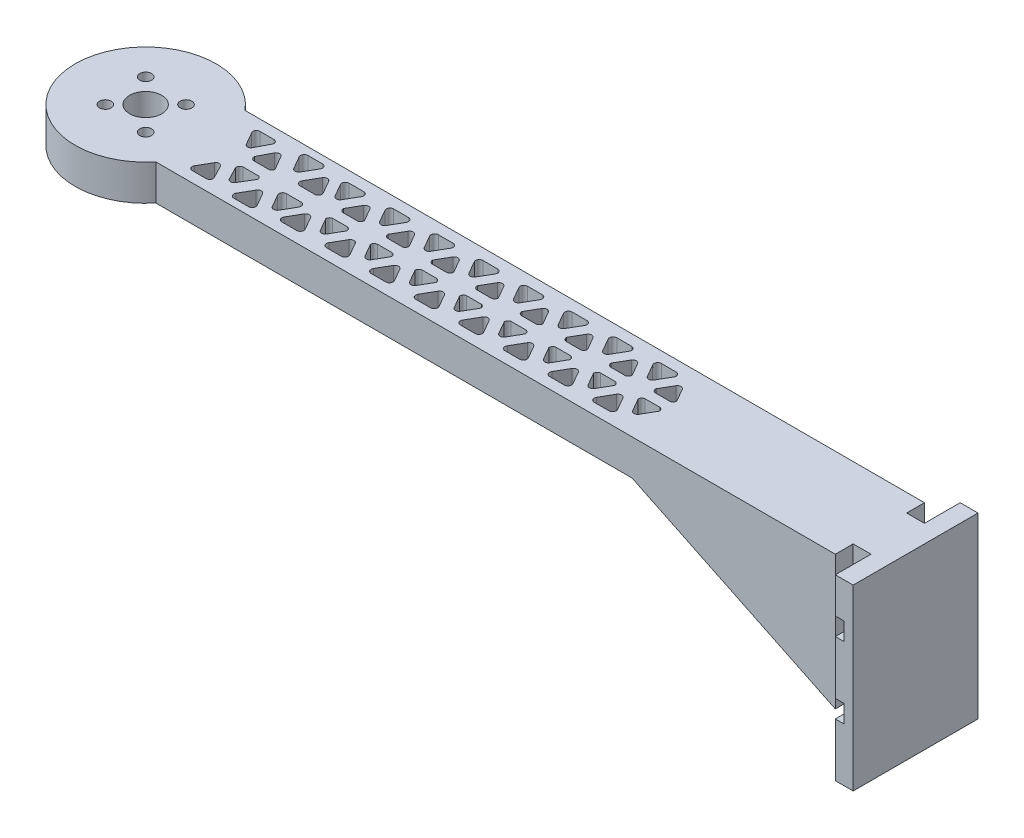
SolidWorks part; units mm, degrees
note: The reader was unsure of these and kept them because the rebuilt part matched: shared geometry of "Sketch2<4>".
ref_plane "Front Plane" through (0, 0, 0) normal (0, 0, 1) x (1, 0, 0)
ref_plane "Top Plane" through (0, 0, 0) normal (0, 1, 0) x (1, 0, 0)
ref_plane "Right Plane" through (0, 0, 0) normal (1, 0, 0) x (0, 0, -1)
sketch "Sketch1" plane through (0, 0, 0) normal (0, 1, 0) x (1, 0, 0)
  line L0 (19.7015, -0.0803) -> (215.7812, -0.0803) construction
  line L1 (15.2517, 12.4197) -> (215.7812, 12.4197)
  line L2 (15.2517, -12.5803) -> (215.7812, -12.5803)
  line L3 (215.7812, 12.4197) -> (215.7812, -12.5803)
  line L4 (22.4549, 9.4197) -> (26.384, 9.4197)
  line L5 (27.2449, 8.0014) -> (25.383, 4.4231)
  line L6 (23.682, 4.3855) -> (21.6147, 7.9638)
  line L7 (29.7182, 6.2554) -> (27.8031, 2.5747)
  line L8 (33.7755, 2.3958) -> (31.5736, 6.0947)
  line L9 (28.7602, 1.4197) -> (33.171, 1.4197)
  line L10 (37.9612, 5.1841) -> (40.0285, 8.7624)
  line L11 (34.1207, 8.7624) -> (36.188, 5.1841)
  line L12 (39.1419, 10.2986) -> (35.0073, 10.2986)
  line L13 (45.3949, 1.819) -> (41.2604, 1.819)
  line L14 (40.3733, 3.3543) -> (42.441, 6.9413)
  line L15 (44.2142, 6.9413) -> (46.2815, 3.363)
  line L16 (47.5213, 9.3393) -> (51.6558, 9.3393)
  line L17 (52.5425, 7.8032) -> (50.4752, 4.2249)
  line L18 (48.702, 4.2249) -> (46.6347, 7.8032)
  line L19 (54.955, 5.982) -> (52.8877, 2.4037)
  line L20 (58.7955, 2.3958) -> (56.7282, 5.982)
  line L21 (53.7743, 1.3393) -> (57.9089, 1.3393)
  line L22 (60.0313, 9.3393) -> (64.1658, 9.3393)
  line L23 (65.0525, 7.8032) -> (62.9852, 4.2249)
  line L24 (61.212, 4.2249) -> (59.1447, 7.8032)
  line L25 (67.465, 5.982) -> (65.3977, 2.4037)
  line L26 (71.3055, 2.3958) -> (69.2382, 5.982)
  line L27 (66.2843, 1.3393) -> (70.4189, 1.3393)
  line L28 (72.5413, 9.3393) -> (76.6758, 9.3393)
  line L29 (77.5625, 7.8032) -> (75.4952, 4.2249)
  line L30 (73.722, 4.2249) -> (71.6547, 7.8032)
  line L31 (79.975, 5.982) -> (77.9077, 2.4037)
  line L32 (83.8155, 2.3958) -> (81.7482, 5.982)
  line L33 (78.7943, 1.3393) -> (82.9289, 1.3393)
  line L34 (85.0513, 9.3393) -> (89.1858, 9.3393)
  line L35 (90.0725, 7.8032) -> (88.0052, 4.2249)
  line L36 (86.232, 4.2249) -> (84.1647, 7.8032)
  line L37 (92.485, 5.982) -> (90.4177, 2.4037)
  line L38 (96.3255, 2.3958) -> (94.2582, 5.982)
  line L39 (91.3043, 1.3393) -> (95.4389, 1.3393)
  line L40 (91.3043, -1.5) -> (95.4389, -1.5)
  line L41 (96.3255, -2.5565) -> (94.2582, -6.1427)
  line L42 (92.485, -6.1427) -> (90.4177, -2.5644)
  line L43 (86.232, -4.3855) -> (84.1647, -7.9638)
  line L44 (90.0725, -7.9638) -> (88.0052, -4.3855)
  line L45 (85.0513, -9.5) -> (89.1858, -9.5)
  line L46 (78.7943, -1.5) -> (82.9289, -1.5)
  line L47 (83.8155, -2.5565) -> (81.7482, -6.1427)
  line L48 (79.975, -6.1427) -> (77.9077, -2.5644)
  line L49 (73.722, -4.3855) -> (71.6547, -7.9638)
  line L50 (77.5625, -7.9638) -> (75.4952, -4.3855)
  line L51 (72.5413, -9.5) -> (76.6758, -9.5)
  line L52 (66.2843, -1.5) -> (70.4189, -1.5)
  line L53 (71.3055, -2.5565) -> (69.2382, -6.1427)
  line L54 (67.465, -6.1427) -> (65.3977, -2.5644)
  line L55 (61.212, -4.3855) -> (59.1447, -7.9638)
  line L56 (65.0525, -7.9638) -> (62.9852, -4.3855)
  line L57 (60.0313, -9.5) -> (64.1658, -9.5)
  line L58 (53.7743, -1.5) -> (57.9089, -1.5)
  line L59 (58.7955, -2.5565) -> (56.7282, -6.1427)
  line L60 (54.955, -6.1427) -> (52.8877, -2.5644)
  line L61 (48.702, -4.3855) -> (46.6347, -7.9638)
  line L62 (52.5425, -7.9638) -> (50.4752, -4.3855)
  line L63 (47.5213, -9.5) -> (51.6558, -9.5)
  line L64 (44.2142, -7.1019) -> (46.2815, -3.5236)
  line L65 (40.3733, -3.5149) -> (42.441, -7.1019)
  line L66 (45.3949, -1.9796) -> (41.2604, -1.9796)
  line L67 (39.1419, -10.4593) -> (35.0073, -10.4593)
  line L68 (34.1207, -8.9231) -> (36.188, -5.3448)
  line L69 (37.9612, -5.3448) -> (40.0285, -8.9231)
  line L70 (28.7602, -1.5803) -> (33.171, -1.5803)
  line L71 (33.7755, -2.5565) -> (31.5736, -6.2554)
  line L72 (29.7182, -6.4161) -> (27.8031, -2.7354)
  line L73 (23.682, -4.5462) -> (21.6147, -8.1245)
  line L74 (27.2449, -8.1621) -> (25.383, -4.5837)
  line L75 (22.4549, -9.5803) -> (26.384, -9.5803)
  line L76 (-0.0803, -16.7095) -> (-0.0803, 16.5488) construction
  line L77 (11.7312, -11.8919) -> (-11.8919, 11.7312) construction
  line L78 (-12.5321, -12.5321) -> (12.3715, 12.3715) construction
  line L79 (97.5613, 9.3393) -> (101.6958, 9.3393)
  line L80 (102.5825, 7.8032) -> (100.5152, 4.2249)
  line L81 (98.742, 4.2249) -> (96.6747, 7.8032)
  line L82 (104.995, 5.982) -> (102.9277, 2.4037)
  line L83 (108.8355, 2.3958) -> (106.7682, 5.982)
  line L84 (103.8143, 1.3393) -> (107.9489, 1.3393)
  line L85 (110.0713, 9.3393) -> (114.2058, 9.3393)
  line L86 (115.0925, 7.8032) -> (113.0252, 4.2249)
  line L87 (111.252, 4.2249) -> (109.1847, 7.8032)
  line L88 (117.505, 5.982) -> (115.4377, 2.4037)
  line L89 (121.3455, 2.3958) -> (119.2782, 5.982)
  line L90 (116.3243, 1.3393) -> (120.4589, 1.3393)
  line L91 (122.5813, 9.3393) -> (126.7158, 9.3393)
  line L92 (127.6025, 7.8032) -> (125.5352, 4.2249)
  line L93 (123.762, 4.2249) -> (121.6947, 7.8032)
  line L94 (130.015, 5.982) -> (127.9477, 2.4037)
  line L95 (133.8555, 2.3958) -> (131.7882, 5.982)
  line L96 (128.8343, 1.3393) -> (132.9689, 1.3393)
  line L97 (135.0913, 9.3393) -> (139.2258, 9.3393)
  line L98 (140.1125, 7.8032) -> (138.0452, 4.2249)
  line L99 (136.272, 4.2249) -> (134.2047, 7.8032)
  line L100 (142.525, 5.982) -> (140.4577, 2.4037)
  line L101 (146.3655, 2.3958) -> (144.2982, 5.982)
  line L102 (141.3443, 1.3393) -> (145.4789, 1.3393)
  line L139 (141.3443, -1.5) -> (145.4789, -1.5)
  line L140 (146.3655, -2.5565) -> (144.2982, -6.1427)
  line L141 (142.525, -6.1427) -> (140.4577, -2.5644)
  line L142 (136.272, -4.3855) -> (134.2047, -7.9638)
  line L143 (140.1125, -7.9638) -> (138.0452, -4.3855)
  line L144 (135.0913, -9.5) -> (139.2258, -9.5)
  line L145 (128.8343, -1.5) -> (132.9689, -1.5)
  line L146 (133.8555, -2.5565) -> (131.7882, -6.1427)
  line L147 (130.015, -6.1427) -> (127.9477, -2.5644)
  line L148 (123.762, -4.3855) -> (121.6947, -7.9638)
  line L149 (127.6025, -7.9638) -> (125.5352, -4.3855)
  line L150 (122.5813, -9.5) -> (126.7158, -9.5)
  line L151 (116.3243, -1.5) -> (120.4589, -1.5)
  line L152 (121.3455, -2.5565) -> (119.2782, -6.1427)
  line L153 (117.505, -6.1427) -> (115.4377, -2.5644)
  line L154 (111.252, -4.3855) -> (109.1847, -7.9638)
  line L155 (115.0925, -7.9638) -> (113.0252, -4.3855)
  line L156 (110.0713, -9.5) -> (114.2058, -9.5)
  line L157 (103.8143, -1.5) -> (107.9489, -1.5)
  line L158 (108.8355, -2.5565) -> (106.7682, -6.1427)
  line L159 (104.995, -6.1427) -> (102.9277, -2.5644)
  line L160 (98.742, -4.3855) -> (96.6747, -7.9638)
  line L161 (102.5825, -7.9638) -> (100.5152, -4.3855)
  line L162 (97.5613, -9.5) -> (101.6958, -9.5)
  line L163 (147.6013, 9.3393) -> (151.7358, 9.3393) [skipped]
  line L164 (152.6225, 7.8032) -> (150.5552, 4.2249) [skipped]
  line L165 (148.782, 4.2249) -> (146.7147, 7.8032) [skipped]
  line L166 (155.035, 5.982) -> (152.9677, 2.4037) [skipped]
  line L167 (158.8755, 2.3958) -> (156.8082, 5.982) [skipped]
  line L168 (153.8543, 1.3393) -> (157.9889, 1.3393) [skipped]
  line L169 (160.1113, 9.3393) -> (164.2458, 9.3393) [skipped]
  line L170 (165.1325, 7.8032) -> (163.0652, 4.2249) [skipped]
  line L171 (161.292, 4.2249) -> (159.2247, 7.8032) [skipped]
  line L172 (167.545, 5.982) -> (165.4777, 2.4037) [skipped]
  line L173 (171.3855, 2.3958) -> (169.3182, 5.982) [skipped]
  line L174 (166.3643, 1.3393) -> (170.4989, 1.3393) [skipped]
  line L175 (172.6213, 9.3393) -> (176.7558, 9.3393) [skipped]
  line L176 (177.6425, 7.8032) -> (175.5752, 4.2249) [skipped]
  line L177 (173.802, 4.2249) -> (171.7347, 7.8032) [skipped]
  line L178 (180.055, 5.982) -> (177.9877, 2.4037) [skipped]
  line L179 (183.8955, 2.3958) -> (181.8282, 5.982) [skipped]
  line L180 (178.8743, 1.3393) -> (183.0089, 1.3393) [skipped]
  circle A0 centre (-0.0803, -0.0803) radius 19.7818
  arc A1 (25.383, 4.4231) -> (23.682, 4.3855) centre (24.5222, 4.871) cw
  arc A2 (22.4549, 9.4197) -> (21.6147, 7.9638) centre (22.4549, 8.4493) ccw
  arc A3 (26.384, 9.4197) -> (27.2449, 8.0014) centre (26.384, 8.4493) cw
  arc A4 (33.171, 1.4197) -> (33.7755, 2.3958) centre (32.7524, 2.3541) ccw
  arc A5 (31.5736, 6.0947) -> (29.7182, 6.2554) centre (30.6092, 5.7508) ccw
  arc A6 (28.7602, 1.4197) -> (27.8031, 2.5747) centre (28.8569, 2.4738) cw
  arc A7 (35.0073, 10.2986) -> (34.1207, 8.7624) centre (35.0073, 9.2747) ccw
  arc A8 (39.1419, 10.2986) -> (40.0285, 8.7624) centre (39.1419, 9.2747) cw
  arc A9 (36.188, 5.1841) -> (37.9612, 5.1841) centre (37.0746, 5.6963) ccw
  arc A10 (45.3949, 1.819) -> (46.2815, 3.363) centre (45.3995, 2.8429) ccw
  arc A11 (42.441, 6.9413) -> (44.2142, 6.9413) centre (43.3276, 6.4291) cw
  arc A12 (41.2604, 1.819) -> (40.3733, 3.3543) centre (41.2604, 2.8429) cw
  arc A13 (50.4752, 4.2249) -> (48.702, 4.2249) centre (49.5886, 4.7371) cw
  arc A14 (47.5213, 9.3393) -> (46.6347, 7.8032) centre (47.5213, 8.3154) ccw
  arc A15 (51.6558, 9.3393) -> (52.5425, 7.8032) centre (51.6558, 8.3154) cw
  arc A16 (57.9089, 1.3393) -> (58.7955, 2.3958) centre (57.7724, 2.3541) ccw
  arc A17 (56.7282, 5.982) -> (54.955, 5.982) centre (55.8416, 5.4698) ccw
  arc A18 (53.7743, 1.3393) -> (52.8877, 2.4037) centre (53.9105, 2.3542) cw
  arc A19 (62.9852, 4.2249) -> (61.212, 4.2249) centre (62.0986, 4.7371) cw
  arc A20 (60.0313, 9.3393) -> (59.1447, 7.8032) centre (60.0313, 8.3154) ccw
  arc A21 (64.1658, 9.3393) -> (65.0525, 7.8032) centre (64.1658, 8.3154) cw
  arc A22 (70.4189, 1.3393) -> (71.3055, 2.3958) centre (70.2824, 2.3541) ccw
  arc A23 (69.2382, 5.982) -> (67.465, 5.982) centre (68.3516, 5.4698) ccw
  arc A24 (66.2843, 1.3393) -> (65.3977, 2.4037) centre (66.4205, 2.3542) cw
  arc A25 (75.4952, 4.2249) -> (73.722, 4.2249) centre (74.6086, 4.7371) cw
  arc A26 (72.5413, 9.3393) -> (71.6547, 7.8032) centre (72.5413, 8.3154) ccw
  arc A27 (76.6758, 9.3393) -> (77.5625, 7.8032) centre (76.6758, 8.3154) cw
  arc A28 (82.9289, 1.3393) -> (83.8155, 2.3958) centre (82.7924, 2.3541) ccw
  arc A29 (81.7482, 5.982) -> (79.975, 5.982) centre (80.8616, 5.4698) ccw
  arc A30 (78.7943, 1.3393) -> (77.9077, 2.4037) centre (78.9305, 2.3542) cw
  arc A31 (88.0052, 4.2249) -> (86.232, 4.2249) centre (87.1186, 4.7371) cw
  arc A32 (85.0513, 9.3393) -> (84.1647, 7.8032) centre (85.0513, 8.3154) ccw
  arc A33 (89.1858, 9.3393) -> (90.0725, 7.8032) centre (89.1858, 8.3154) cw
  arc A34 (95.4389, 1.3393) -> (96.3255, 2.3958) centre (95.3024, 2.3541) ccw
  arc A35 (94.2582, 5.982) -> (92.485, 5.982) centre (93.3716, 5.4698) ccw
  arc A36 (91.3043, 1.3393) -> (90.4177, 2.4037) centre (91.4405, 2.3542) cw
  arc A37 (91.3043, -1.5) -> (90.4177, -2.5644) centre (91.4405, -2.5148) ccw
  arc A38 (94.2582, -6.1427) -> (92.485, -6.1427) centre (93.3716, -5.6305) cw
  arc A39 (95.4389, -1.5) -> (96.3255, -2.5565) centre (95.3024, -2.5148) cw
  arc A40 (89.1858, -9.5) -> (90.0725, -7.9638) centre (89.1858, -8.4761) ccw
  arc A41 (85.0513, -9.5) -> (84.1647, -7.9638) centre (85.0513, -8.4761) cw
  arc A42 (88.0052, -4.3855) -> (86.232, -4.3855) centre (87.1186, -4.8978) ccw
  arc A43 (78.7943, -1.5) -> (77.9077, -2.5644) centre (78.9305, -2.5148) ccw
  arc A44 (81.7482, -6.1427) -> (79.975, -6.1427) centre (80.8616, -5.6305) cw
  arc A45 (82.9289, -1.5) -> (83.8155, -2.5565) centre (82.7924, -2.5148) cw
  arc A46 (76.6758, -9.5) -> (77.5625, -7.9638) centre (76.6758, -8.4761) ccw
  arc A47 (72.5413, -9.5) -> (71.6547, -7.9638) centre (72.5413, -8.4761) cw
  arc A48 (75.4952, -4.3855) -> (73.722, -4.3855) centre (74.6086, -4.8978) ccw
  arc A49 (66.2843, -1.5) -> (65.3977, -2.5644) centre (66.4205, -2.5148) ccw
  arc A50 (69.2382, -6.1427) -> (67.465, -6.1427) centre (68.3516, -5.6305) cw
  arc A51 (70.4189, -1.5) -> (71.3055, -2.5565) centre (70.2824, -2.5148) cw
  arc A52 (64.1658, -9.5) -> (65.0525, -7.9638) centre (64.1658, -8.4761) ccw
  arc A53 (60.0313, -9.5) -> (59.1447, -7.9638) centre (60.0313, -8.4761) cw
  arc A54 (62.9852, -4.3855) -> (61.212, -4.3855) centre (62.0986, -4.8978) ccw
  arc A55 (53.7743, -1.5) -> (52.8877, -2.5644) centre (53.9105, -2.5148) ccw
  arc A56 (56.7282, -6.1427) -> (54.955, -6.1427) centre (55.8416, -5.6305) cw
  arc A57 (57.9089, -1.5) -> (58.7955, -2.5565) centre (57.7724, -2.5148) cw
  arc A58 (51.6558, -9.5) -> (52.5425, -7.9638) centre (51.6558, -8.4761) ccw
  arc A59 (47.5213, -9.5) -> (46.6347, -7.9638) centre (47.5213, -8.4761) cw
  arc A60 (50.4752, -4.3855) -> (48.702, -4.3855) centre (49.5886, -4.8978) ccw
  arc A61 (41.2604, -1.9796) -> (40.3733, -3.5149) centre (41.2604, -3.0036) ccw
  arc A62 (42.441, -7.1019) -> (44.2142, -7.1019) centre (43.3276, -6.5897) ccw
  arc A63 (45.3949, -1.9796) -> (46.2815, -3.5236) centre (45.3995, -3.0036) cw
  arc A64 (36.188, -5.3448) -> (37.9612, -5.3448) centre (37.0746, -5.857) cw
  arc A65 (39.1419, -10.4593) -> (40.0285, -8.9231) centre (39.1419, -9.4353) ccw
  arc A66 (35.0073, -10.4593) -> (34.1207, -8.9231) centre (35.0073, -9.4353) cw
  arc A67 (28.7602, -1.5803) -> (27.8031, -2.7354) centre (28.8569, -2.6345) ccw
  arc A68 (31.5736, -6.2554) -> (29.7182, -6.4161) centre (30.6092, -5.9115) cw
  arc A69 (33.171, -1.5803) -> (33.7755, -2.5565) centre (32.7524, -2.5148) cw
  arc A70 (26.384, -9.5803) -> (27.2449, -8.1621) centre (26.384, -8.61) ccw
  arc A71 (22.4549, -9.5803) -> (21.6147, -8.1245) centre (22.4549, -8.61) cw
  arc A72 (25.383, -4.5837) -> (23.682, -4.5462) centre (24.5222, -5.0316) ccw
  circle A73 centre (-6.7979, 6.6372) radius 1.65
  circle A74 centre (5.5765, 5.5765) radius 1.65
  circle A75 centre (6.6372, -6.7979) radius 1.65
  circle A76 centre (-5.7372, -5.7372) radius 1.65
  circle A77 centre (-0.0803, -0.0803) radius 4.5
  arc A78 (100.5152, 4.2249) -> (98.742, 4.2249) centre (99.6286, 4.7371) cw
  arc A79 (97.5613, 9.3393) -> (96.6747, 7.8032) centre (97.5613, 8.3154) ccw
  arc A80 (101.6958, 9.3393) -> (102.5825, 7.8032) centre (101.6958, 8.3154) cw
  arc A81 (107.9489, 1.3393) -> (108.8355, 2.3958) centre (107.8124, 2.3541) ccw
  arc A82 (106.7682, 5.982) -> (104.995, 5.982) centre (105.8816, 5.4698) ccw
  arc A83 (103.8143, 1.3393) -> (102.9277, 2.4037) centre (103.9505, 2.3542) cw
  arc A84 (113.0252, 4.2249) -> (111.252, 4.2249) centre (112.1386, 4.7371) cw
  arc A85 (110.0713, 9.3393) -> (109.1847, 7.8032) centre (110.0713, 8.3154) ccw
  arc A86 (114.2058, 9.3393) -> (115.0925, 7.8032) centre (114.2058, 8.3154) cw
  arc A87 (120.4589, 1.3393) -> (121.3455, 2.3958) centre (120.3224, 2.3541) ccw
  arc A88 (119.2782, 5.982) -> (117.505, 5.982) centre (118.3916, 5.4698) ccw
  arc A89 (116.3243, 1.3393) -> (115.4377, 2.4037) centre (116.4605, 2.3542) cw
  arc A90 (125.5352, 4.2249) -> (123.762, 4.2249) centre (124.6486, 4.7371) cw
  arc A91 (122.5813, 9.3393) -> (121.6947, 7.8032) centre (122.5813, 8.3154) ccw
  arc A92 (126.7158, 9.3393) -> (127.6025, 7.8032) centre (126.7158, 8.3154) cw
  arc A93 (132.9689, 1.3393) -> (133.8555, 2.3958) centre (132.8324, 2.3541) ccw
  arc A94 (131.7882, 5.982) -> (130.015, 5.982) centre (130.9016, 5.4698) ccw
  arc A95 (128.8343, 1.3393) -> (127.9477, 2.4037) centre (128.9705, 2.3542) cw
  arc A96 (138.0452, 4.2249) -> (136.272, 4.2249) centre (137.1586, 4.7371) cw
  arc A97 (135.0913, 9.3393) -> (134.2047, 7.8032) centre (135.0913, 8.3154) ccw
  arc A98 (139.2258, 9.3393) -> (140.1125, 7.8032) centre (139.2258, 8.3154) cw
  arc A99 (145.4789, 1.3393) -> (146.3655, 2.3958) centre (145.3424, 2.3541) ccw
  arc A100 (144.2982, 5.982) -> (142.525, 5.982) centre (143.4116, 5.4698) ccw
  arc A101 (141.3443, 1.3393) -> (140.4577, 2.4037) centre (141.4805, 2.3542) cw
  arc A138 (141.3443, -1.5) -> (140.4577, -2.5644) centre (141.4805, -2.5148) ccw
  arc A139 (144.2982, -6.1427) -> (142.525, -6.1427) centre (143.4116, -5.6305) cw
  arc A140 (145.4789, -1.5) -> (146.3655, -2.5565) centre (145.3424, -2.5148) cw
  arc A141 (139.2258, -9.5) -> (140.1125, -7.9638) centre (139.2258, -8.4761) ccw
  arc A142 (135.0913, -9.5) -> (134.2047, -7.9638) centre (135.0913, -8.4761) cw
  arc A143 (138.0452, -4.3855) -> (136.272, -4.3855) centre (137.1586, -4.8978) ccw
  arc A144 (128.8343, -1.5) -> (127.9477, -2.5644) centre (128.9705, -2.5148) ccw
  arc A145 (131.7882, -6.1427) -> (130.015, -6.1427) centre (130.9016, -5.6305) cw
  arc A146 (132.9689, -1.5) -> (133.8555, -2.5565) centre (132.8324, -2.5148) cw
  arc A147 (126.7158, -9.5) -> (127.6025, -7.9638) centre (126.7158, -8.4761) ccw
  arc A148 (122.5813, -9.5) -> (121.6947, -7.9638) centre (122.5813, -8.4761) cw
  arc A149 (125.5352, -4.3855) -> (123.762, -4.3855) centre (124.6486, -4.8978) ccw
  arc A150 (116.3243, -1.5) -> (115.4377, -2.5644) centre (116.4605, -2.5148) ccw
  arc A151 (119.2782, -6.1427) -> (117.505, -6.1427) centre (118.3916, -5.6305) cw
  arc A152 (120.4589, -1.5) -> (121.3455, -2.5565) centre (120.3224, -2.5148) cw
  arc A153 (114.2058, -9.5) -> (115.0925, -7.9638) centre (114.2058, -8.4761) ccw
  arc A154 (110.0713, -9.5) -> (109.1847, -7.9638) centre (110.0713, -8.4761) cw
  arc A155 (113.0252, -4.3855) -> (111.252, -4.3855) centre (112.1386, -4.8978) ccw
  arc A156 (103.8143, -1.5) -> (102.9277, -2.5644) centre (103.9505, -2.5148) ccw
  arc A157 (106.7682, -6.1427) -> (104.995, -6.1427) centre (105.8816, -5.6305) cw
  arc A158 (107.9489, -1.5) -> (108.8355, -2.5565) centre (107.8124, -2.5148) cw
  arc A159 (101.6958, -9.5) -> (102.5825, -7.9638) centre (101.6958, -8.4761) ccw
  arc A160 (97.5613, -9.5) -> (96.6747, -7.9638) centre (97.5613, -8.4761) cw
  arc A161 (100.5152, -4.3855) -> (98.742, -4.3855) centre (99.6286, -4.8978) ccw
  arc A162 (150.5552, 4.2249) -> (148.782, 4.2249) centre (149.6686, 4.7371) cw [skipped]
  arc A163 (147.6013, 9.3393) -> (146.7147, 7.8032) centre (147.6013, 8.3154) ccw [skipped]
  arc A164 (151.7358, 9.3393) -> (152.6225, 7.8032) centre (151.7358, 8.3154) cw [skipped]
  arc A165 (157.9889, 1.3393) -> (158.8755, 2.3958) centre (157.8524, 2.3541) ccw [skipped]
  arc A166 (156.8082, 5.982) -> (155.035, 5.982) centre (155.9216, 5.4698) ccw [skipped]
  arc A167 (153.8543, 1.3393) -> (152.9677, 2.4037) centre (153.9905, 2.3542) cw [skipped]
  arc A168 (163.0652, 4.2249) -> (161.292, 4.2249) centre (162.1786, 4.7371) cw [skipped]
  arc A169 (160.1113, 9.3393) -> (159.2247, 7.8032) centre (160.1113, 8.3154) ccw [skipped]
  arc A170 (164.2458, 9.3393) -> (165.1325, 7.8032) centre (164.2458, 8.3154) cw [skipped]
  arc A171 (170.4989, 1.3393) -> (171.3855, 2.3958) centre (170.3624, 2.3541) ccw [skipped]
  arc A172 (169.3182, 5.982) -> (167.545, 5.982) centre (168.4316, 5.4698) ccw [skipped]
  arc A173 (166.3643, 1.3393) -> (165.4777, 2.4037) centre (166.5005, 2.3542) cw [skipped]
  arc A174 (175.5752, 4.2249) -> (173.802, 4.2249) centre (174.6886, 4.7371) cw [skipped]
  arc A175 (172.6213, 9.3393) -> (171.7347, 7.8032) centre (172.6213, 8.3154) ccw [skipped]
  arc A176 (176.7558, 9.3393) -> (177.6425, 7.8032) centre (176.7558, 8.3154) cw [skipped]
  arc A177 (183.0089, 1.3393) -> (183.8955, 2.3958) centre (182.8724, 2.3541) ccw [skipped]
  arc A178 (181.8282, 5.982) -> (180.055, 5.982) centre (180.9416, 5.4698) ccw [skipped]
  arc A179 (178.8743, 1.3393) -> (177.9877, 2.4037) centre (179.0105, 2.3542) cw [skipped]
  point P5 (-0.0803, -0.0803)
  point P8 (-0.0803, -0.0803)
  point P55 (30.6092, 5.7508)
  point P66 (37.0746, 5.6963)
  point P74 (43.3276, 6.4291)
  point P93 (55.8416, 5.4698)
  point P112 (68.3516, 5.4698)
  point P131 (80.8616, 5.4698)
  point P150 (93.3716, 5.4698)
  point P239 (93.3716, -5.6305)
  point P240 (80.8616, -5.6305)
  point P241 (68.3516, -5.6305)
  point P242 (55.8416, -5.6305)
  point P243 (43.3276, -6.5897)
  point P244 (37.0746, -5.857)
  point P245 (30.6092, -5.9115)
  point P247 (-0.0803, -0.0803)
  point P256 (180.9416, 5.4698)
  point P257 (168.4316, 5.4698)
  point P276 (105.8816, 5.4698)
  point P295 (118.3916, 5.4698)
  point P314 (130.9016, 5.4698)
  point P333 (143.4116, 5.4698)
  point P334 (155.9216, 5.4698)
  point P518 (143.4116, -5.6305)
  point P519 (130.9016, -5.6305)
  point P520 (118.3916, -5.6305)
  point P521 (105.8816, -5.6305)
  dimension "D7" = 3.3
  dimension "D8" = 3.3
  dimension "D9" = 3.3
  dimension "D10" = 3.3
  dimension "D15" = 9
  dimension "D1" = 3
  dimension "D2" = 3
  dimension "D3" = 25
  dimension "D4" = 3
  dimension "D5" = 45
  dimension "D6" = 90
  dimension "D11" = 9.5
  dimension "D12" = 9.5
  dimension "D13" = 8
  dimension "D14" = 8
  dimension "D16" = 8
extrude "Boss-Extrude1" add sketch "Sketch1" along normal blind 10
sketch "Sketch2" plane through (0, 10, 0) normal (0, 1, 0) x (1, 0, 0)
  line L0 (215.7812, 12.4197) -> (215.7812, 17.4197)
  line L1 (215.7812, 17.4197) -> (210.7812, 17.4197)
  line L2 (210.7812, 17.4197) -> (210.7812, -12.5803)
  line L3 (15.2517, -12.5803) -> (215.7812, -12.5803) construction
  line L4 (210.7812, -12.5803) -> (210.7812, -17.5803)
  line L5 (210.7812, -17.5803) -> (215.7812, -17.5803)
  line L6 (215.7812, -17.5803) -> (215.7812, -12.5803)
  line L7 (215.7812, -12.5803) -> (215.7812, 12.4197)
  line L8 (210.7812, -12.5803) -> (205.7812, -12.5803)
  line L17 (205.7812, -12.5803) -> (205.7812, -7.5803)
  line L18 (205.7812, -7.5803) -> (210.7812, -7.5803)
  line L19 (205.7812, 12.4197) -> (205.7812, 7.4197)
  line L20 (15.2517, 12.4197) -> (215.7812, 12.4197) construction
  line L21 (205.7812, 7.4197) -> (210.7812, 7.4197)
  line L22 (205.7812, 12.4197) -> (210.7812, 12.4197)
  line L23 (210.7812, 12.4197) -> (210.7812, 7.4197)
  line L24 (210.7812, -7.5803) -> (210.7812, -12.5803)
  dimension "D1" = 5
  dimension "D2" = 5
  dimension "D3" = 5
  dimension "D4" = 5
  dimension "D5" = 5
  dimension "D6" = 5
extrude "Boss-Extrude2" add sketch "Sketch2" against normal blind 50 contours L6 L7 L0 L1 L2 L4 L5
sketch "Sketch3" plane through (0, 0, 12.5803) normal (0, 0, 1) x (1, 0, 0)
  line L8 (210.7812, 0) -> (148.7812, 0)
  line L9 (15.2517, 0) -> (210.7812, 0) construction
  line L10 (210.7812, 0) -> (210.7812, -30)
  line L11 (210.7812, -40) -> (210.7812, 10) construction
  line L12 (210.7812, -30) -> (148.7812, 0)
extrude "Boss-Extrude3" add sketch "Sketch3" against normal up to surface (25 mm away) up to face at (113.0165, 5, -12.4197)
extrude "Cut-Extrude1" cut sketch "Sketch2<4>" against normal up to surface (40 mm away) contours L22 L19 L21 L2 | L18 L17 L8 L2
sketch "Sketch2<4>" plane through (0, 10, 0) normal (0, 1, 0) x (1, 0, 0) same geometry as "Sketch2"
sketch "Sketch4" plane through (0, 0, 17.5803) normal (0, 0, 1) x (1, 0, 0)
  line L0 (210.7812, -30) -> (210.7812, 10) construction
  line L1 (208.2812, -5) -> (213.2812, -5)
  line L2 (208.2812, -5) -> (208.2812, 0)
  line L3 (208.2812, 0) -> (213.2812, 0)
  line L4 (213.2812, -5) -> (213.2812, 0)
  line L5 (208.2812, -5) -> (213.2812, 0) construction
  line L6 (208.2812, 0) -> (213.2812, -5) construction
  line L8 (208.2812, -25) -> (213.2812, -25)
  line L9 (208.2812, -25) -> (208.2812, -20)
  line L10 (208.2812, -20) -> (213.2812, -20)
  line L11 (213.2812, -25) -> (213.2812, -20)
  line L12 (208.2812, -25) -> (213.2812, -20) construction
  line L13 (208.2812, -20) -> (213.2812, -25) construction
  point P0 (210.7812, -2.5)
  point P7 (210.7812, -22.5)
  line M7 (210.7812, 10) -> (210.7812, -40)
  dimension "D1" = 5
  dimension "D2" = 5
  dimension "D3" = 5
  dimension "D4" = 5
  dimension "D5" = 10
  dimension "D6" = 15
extrude "Cut-Extrude2" cut sketch "Sketch4" against normal up to surface (35 mm away) contours L10 L9 L8 M7 | L8 L11 L10 M7 | L3 L2 L1 M7 | L1 L4 L3 M7 up to face at (213.2812, -15, -17.4197)
